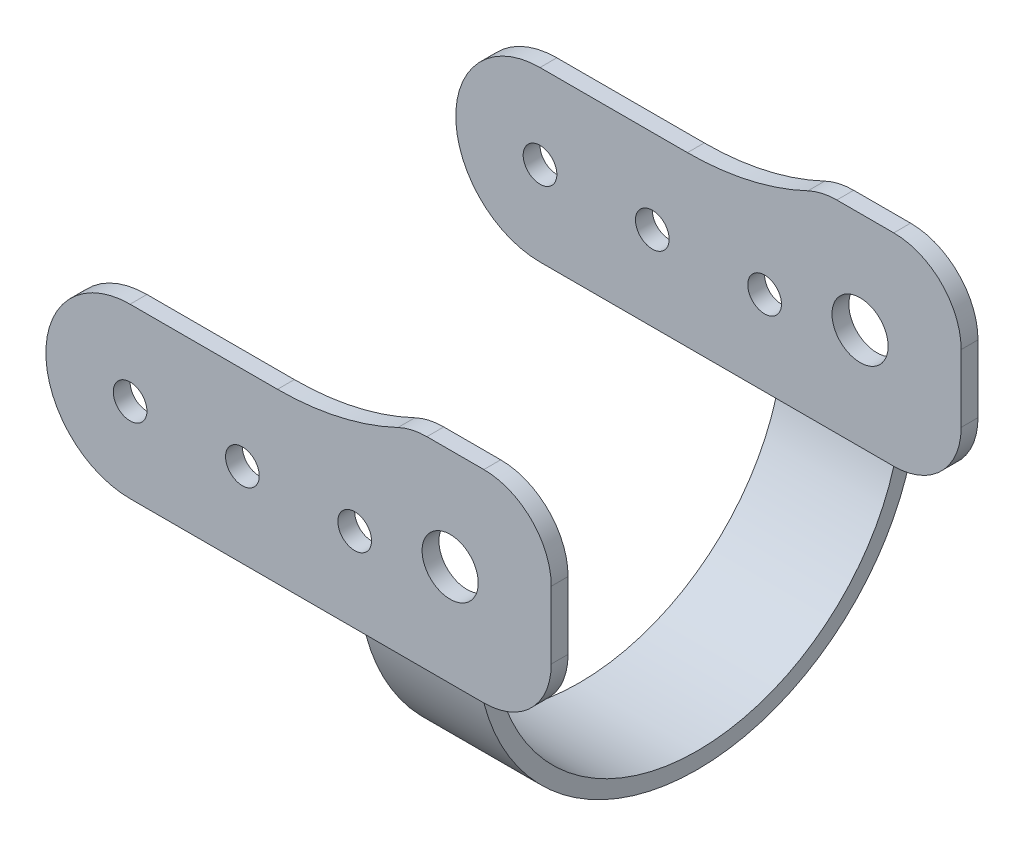
SolidWorks part; units mm, degrees
ref_plane "Front Plane" through (0, 0, 0) normal (0, 0, 1) x (1, 0, 0)
ref_plane "Top Plane" through (0, 0, 0) normal (0, 1, 0) x (1, 0, 0)
ref_plane "Right Plane" through (0, 0, 0) normal (1, 0, 0) x (0, 0, -1)
sketch "Sketch1" plane through (0, 0, 0) normal (0, 0, 1) x (1, 0, 0)
  line L0 (0, 15) -> (26.2513, 15)
  line L1 (63, -15) -> (0, -15)
  line L5 (52.8596, 21) -> (63, 21)
  line L6 (75, -3) -> (75, 9)
  arc A1 (0, -15) -> (0, 15) centre (0, 0) cw
  arc A2 (26.2513, 15) -> (47.7096, 19.8387) centre (26.2513, 65) ccw
  arc A3 (63, -15) -> (75, -3) centre (63, -3) ccw
  arc A4 (63, 21) -> (75, 9) centre (63, 9) cw
  arc A5 (52.8596, 21) -> (47.7096, 19.8387) centre (52.8596, 9) ccw
  point P3 (75, -15)
  point P15 (75, 21)
  point P18 (50, 21)
  dimension "D2" = 15
  dimension "D4" = 50
  dimension "D1" = 12
  dimension "D3" = 36
  dimension "D5" = 25
  dimension "D6" = 75
extrude "Boss-Extrude1" add sketch "Sketch1" along normal blind 3 from offset 35
sketch "Sketch2" plane through (0, 0, 38) normal (0, 0, 1) x (1, 0, 0)
  line L0 (-15, 0) -> (-15, -15) construction
  line L1 (75, -3) -> (75, 9) construction
  line L3 (30, -15) -> (30, 0) construction
  line L5 (0, -15) -> (63, -15) construction
  line L6 (0, 0) -> (20, 0) construction
  line L7 (20, 0) -> (40, 0) construction
  line L8 (-15, -15) -> (0, -15) construction
  circle A0 centre (0, 0) radius 3
  circle A2 centre (20, 0) radius 3
  circle A5 centre (40, 0) radius 3
  arc A6 (0, 15) -> (0, -15) centre (0, 0) ccw construction
  dimension "D1" = 6
extrude "Cut-Extrude1" cut sketch "Sketch2" against normal up to surface (3 mm away) up to face at (43.6662, 7.4368, 35)
sketch "Sketch3" plane through (0, 0, 38) normal (0, 0, 1) x (1, 0, 0)
  line L0 (75, -3) -> (75, 9) construction
  line L2 (57, 3) -> (75, 3) construction
  circle A0 centre (57, 3) radius 5
  dimension "D1" = 10
  dimension "D2" = 18
extrude "Cut-Extrude2" cut sketch "Sketch3" against normal up to surface (3 mm away) up to face at (3, 0, 35)
sketch "Sketch4" plane through (0, 0, 0) normal (1, 0, 0) x (0, 0, -1)
  line L0 (-38, -15) -> (-35, -15)
  line L1 (35, -15) -> (38, -15)
  arc A0 (-35, -15) -> (35, -15) centre (0, -5) ccw
  arc A1 (-38, -15) -> (38, -15) centre (0, -5) ccw
  dimension "D1" = 5
extrude "Boss-Extrude2" add sketch "Sketch4" along normal blind 21 from offset 42
mirror "Mirror1" about plane through (0, 0, 0) normal (0, 0, 1) of "Cut-Extrude1", "Cut-Extrude2", "Boss-Extrude1"
